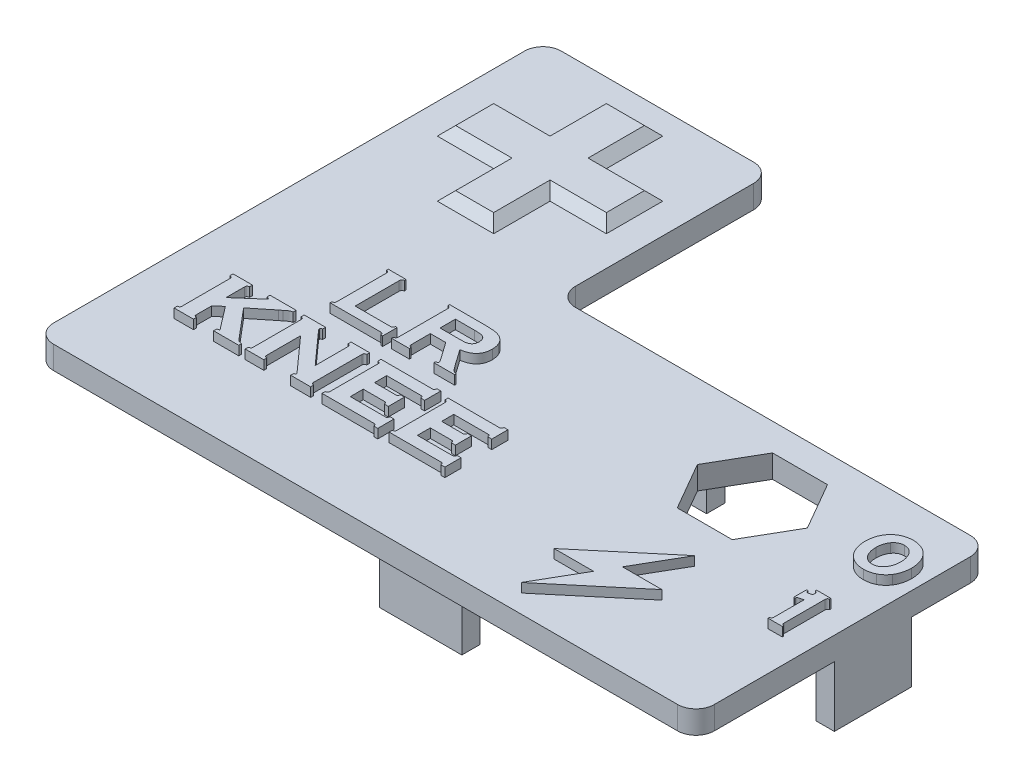
SolidWorks part; units mm, degrees
ref_plane "Front" through (0, 0, 0) normal (0, 0, 1) x (1, 0, 0)
ref_plane "Top" through (0, 0, 0) normal (0, 1, 0) x (1, 0, 0)
ref_plane "Right" through (0, 0, 0) normal (1, 0, 0) x (0, 0, -1)
sketch "Sketch1" plane through (0, 0, 0) normal (0, 1, 0) x (1, 0, 0)
  line L0 (-36.05, 15.975) -> (-36.05, 39.425)
  line L1 (-36.05, -15.975) -> (36.05, -15.975)
  line L2 (-36.05, -15.975) -> (-36.05, 15.975)
  line L3 (-11.05, 15.975) -> (36.05, 15.975)
  line L4 (36.05, -15.975) -> (36.05, 15.975)
  line L5 (-36.05, -15.975) -> (36.05, 15.975) construction
  line L6 (-36.05, 15.975) -> (36.05, -15.975) construction
  line L7 (-36.05, 39.425) -> (-11.05, 39.425)
  line L8 (-11.05, 39.425) -> (-11.05, 15.975)
  point P0 (0, 0)
  dimension "D1" = 31.95
  dimension "D2" = 72.1
  dimension "D3" = 25
  dimension "D4" = 55.4
extrude "Boss-Extrude1" add sketch "Sketch1" along normal blind 2.5
fillet "Fillet1" radius 2 6 edges at (36.05, 1.25, -15.975) (36.05, 1.25, 15.975) (-36.05, 1.25, 15.975) (-11.05, 1.25, -15.975) (-11.05, 1.25, -39.425) (-36.05, 1.25, -39.425)
sketch "Sketch2" plane through (0, 0, 0) normal (0, -1, 0) x (1, 0, 0)
  line L0 (36.05, 13.975) -> (36.05, -13.975) construction
  line L1 (34.05, -7.525) -> (36.05, -7.525)
  line L2 (34.05, -7.525) -> (34.05, 0.875)
  line L3 (34.05, 0.875) -> (36.05, 0.875)
  line L4 (36.05, -7.525) -> (36.05, 0.875)
  line L5 (34.05, -7.525) -> (36.05, 0.875) construction
  line L6 (34.05, 0.875) -> (36.05, -7.525) construction
  line L7 (35.05, -7.575) -> (35.05, 0.925) construction
  line L8 (35.05, 0.925) -> (35.05, 15.975) construction
  line L9 (-34.05, 15.975) -> (34.05, 15.975) construction
  line L10 (34.05, -15.975) -> (-9.05, -15.975) construction
  line L11 (8.5, -14.725) -> (-0.5, -14.725)
  line L12 (8.5, -14.725) -> (8.5, -12.725)
  line L13 (8.5, -12.725) -> (-0.5, -12.725)
  line L14 (-0.5, -14.725) -> (-0.5, -12.725)
  line L15 (8.5, -14.725) -> (-0.5, -12.725) construction
  line L16 (8.5, -12.725) -> (-0.5, -14.725) construction
  line L17 (8.5, 11.975) -> (-0.5, 11.975)
  line L18 (8.5, 11.975) -> (8.5, 13.975)
  line L19 (8.5, 13.975) -> (-0.5, 13.975)
  line L20 (-0.5, 11.975) -> (-0.5, 13.975)
  line L21 (8.5, 11.975) -> (-0.5, 13.975) construction
  line L22 (8.5, 13.975) -> (-0.5, 11.975) construction
  line L23 (0, 0) -> (-50000, 0) construction
  point P0 (35.05, -3.325)
  point P7 (35.05, -3.325)
  point P13 (4, -13.725)
  point P18 (4, 12.975)
  dimension "D1" = 2
  dimension "D2" = 8.4
  dimension "D3" = 15.05
  dimension "D4" = 8.5
  dimension "D5" = 2
  dimension "D6" = 1.25
  dimension "D7" = 2
  dimension "D8" = 0.5
  dimension "D9" = 9
extrude "Boss-Extrude2" add sketch "Sketch2" along normal blind 6.6
sketch "Sketch3" plane through (0, 2.5, 0) normal (0, 1, 0) x (1, 0, 0)
  line L0 (-22.8, 2.025) -> (-7.8, 2.025) construction
  line L1 (-34.05, -6.975) -> (3.45, -6.975) construction
  line L2 (29.55, 6.025) -> (36.05, 6.025) construction
  line L9 (21.9141, -1.975) -> (19.0274, -6.975)
  line L11 (17.8726, -8.975) -> (14.9859, -13.975)
  line L12 (14.9859, -13.975) -> (23.3282, -6.975)
  line L13 (23.3282, -6.975) -> (19.0274, -6.975)
  line L14 (21.9141, -1.975) -> (13.5718, -8.975)
  line L15 (13.5718, -8.975) -> (17.8726, -8.975)
  line L16 (12.7, -15.975) -> (12.7, 0.025) construction
  line L17 (-34.05, -15.975) -> (34.05, -15.975) construction
  line L18 (12.7, 0.025) -> (24.2, 0.025) construction
  line L19 (24.2, 0.025) -> (24.2, -15.975) construction
  line L20 (24.2, -15.975) -> (12.7, -15.975) construction
  line L21 (36.05, -13.975) -> (36.05, 13.975) construction
  line L22 (21.9141, -1.975) -> (14.9859, -13.975) construction
  line L23 (-26.625, 36.925) -> (-20.475, 36.925)
  line L24 (-20.475, 36.925) -> (-20.475, 30.775)
  line L25 (-36.05, 37.425) -> (-36.05, -13.975) construction
  line L26 (-20.475, 30.775) -> (-14.325, 30.775)
  line L27 (-14.325, 30.775) -> (-14.325, 24.625)
  line L28 (-14.325, 24.625) -> (-20.475, 24.625)
  line L29 (-20.475, 24.625) -> (-20.475, 18.475)
  line L30 (-20.475, 18.475) -> (-26.625, 18.475)
  line L31 (-26.625, 18.475) -> (-26.625, 24.625)
  line L32 (-26.625, 24.625) -> (-32.775, 24.625)
  line L33 (-32.775, 24.625) -> (-32.775, 30.775)
  line L34 (-32.775, 30.775) -> (-26.625, 30.775)
  line L35 (-26.625, 30.775) -> (-26.625, 36.925)
  line L36 (-11.05, 27.7) -> (-36.05, 27.7) construction
  line L37 (-11.05, 17.975) -> (-11.05, 37.425) construction
  line L38 (-36.05, 37.425) -> (-36.05, -13.975) construction
  line L39 (-13.05, 39.425) -> (-34.05, 39.425) construction
  text T0 "<b>KNEE</b>" font "Copperplate Gothic Bold" height 6.35
  text T1 "LR" font "Copperplate Gothic Bold" height 6.35
  text T2 "0\r\n1" font "Copperplate Gothic Bold" height in points 26
  point P18 (18.45, -7.975)
  point P19 (18.45, 0.025)
  point P20 (12.7, -7.975)
  point P38 (-32.775, 27.7)
  point P43 (-15.3, 2.025)
  point P44 (-15.3, -6.975)
  point P50 (-23.55, 36.925)
  point P51 (-23.55, 27.7)
  dimension "D1" = 40
  dimension "D2" = 20
  dimension "D3" = 2
  dimension "D4" = 5
  dimension "D5" = 11.85
  dimension "D6" = 23.35
  dimension "D7" = 2
  dimension "D8" = 6.5
  dimension "D9" = 22
  dimension "D10" = 18
  dimension "D11" = 2
  dimension "D12" = 9
  dimension "D13" = 37.5
  dimension "D14" = 15
  dimension "D15" = 2.5
extrude "Boss-Extrude3" add sketch "Sketch3" along normal blind 1
sketch "Sketch4" plane through (0, 2.5, 0) normal (0, 1, 0) x (1, 0, 0)
  line L5 (34.05, 15.975) -> (-9.05, 15.975) construction
  line L7 (18.45, 2.5827) -> (18.45, -15.975) construction
  line L9 (21.45, 2.5827) -> (24.45, 7.7788)
  line L10 (24.45, 7.7788) -> (21.45, 12.975)
  line L11 (21.45, 12.975) -> (15.45, 12.975)
  line L12 (15.45, 12.975) -> (12.45, 7.7788)
  line L13 (12.45, 7.7788) -> (15.45, 2.5827)
  line L14 (15.45, 2.5827) -> (21.45, 2.5827)
  line L15 (24.2, -15.975) -> (12.7, -15.975) construction
  circle A0 centre (18.45, 7.7788) radius 5.1962 construction
  dimension "D1" = 3
  dimension "D2" = 6
extrude "Cut-Extrude1" cut sketch "Sketch4" against normal up to vertex (2.5 mm away) up to point (34.05, 0, 15.975)
chamfer "Chamfer1" distance 1 angle 45 12 edges at (-23.55, 3.5, -36.925) (-20.475, 3.5, -33.85) (-17.4, 3.5, -30.775) (-14.325, 3.5, -27.7) (-17.4, 3.5, -24.625) (-20.475, 3.5, -21.55) (-23.55, 3.5, -18.475) (-26.625, 3.5, -21.55) (-29.7, 3.5, -24.625) (-32.775, 3.5, -27.7) (-29.7, 3.5, -30.775) (-26.625, 3.5, -33.85)
